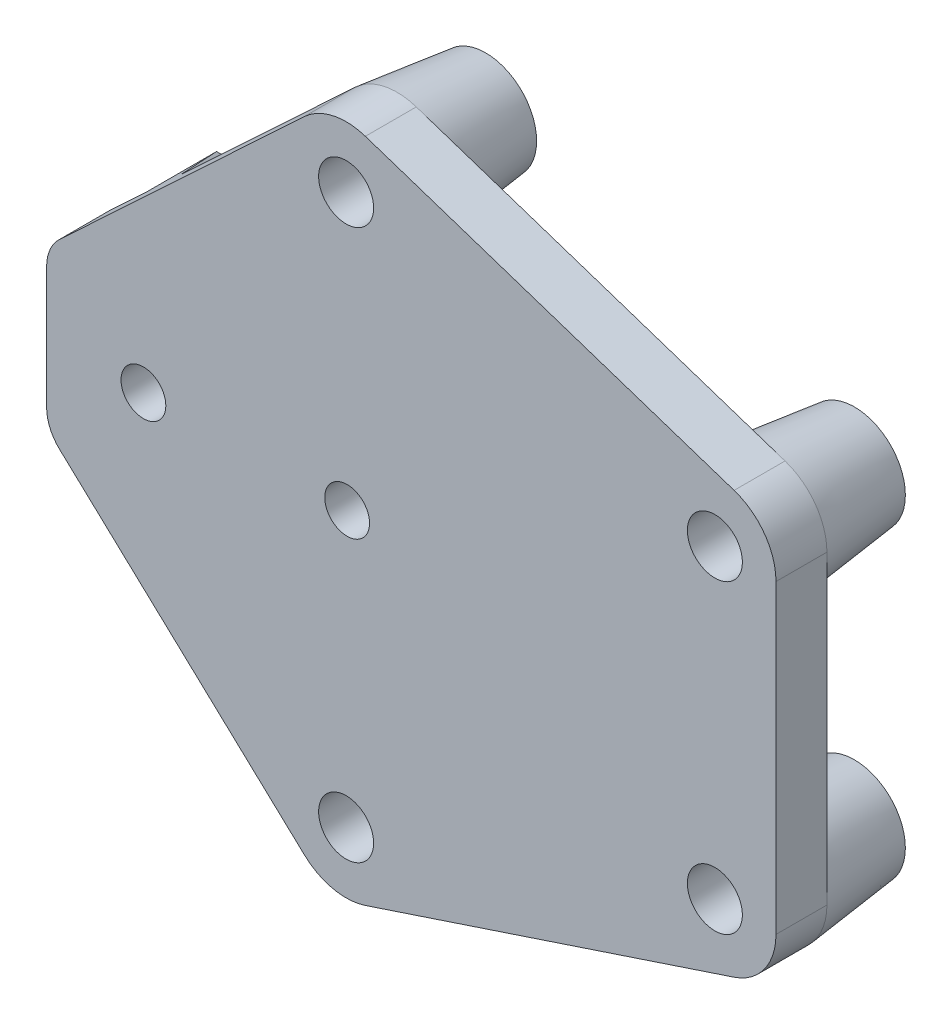
SolidWorks part; units mm, degrees
note: '?' marks a value the reader was unsure of. The reader was unsure of these and kept them because the rebuilt part matched: shared geometry of "草图4<3>", "草图1<4>".
ref_plane "前视基准面" through (0, 0, 0) normal (0, 0, 1) x (1, 0, 0)
ref_plane "上视基准面" through (0, 0, 0) normal (0, 1, 0) x (1, 0, 0)
ref_plane "右视基准面" through (0, 0, 0) normal (1, 0, 0) x (0, 0, -1)
sketch "草图1" plane through (0, 0, 0) normal (0, 0, 1) x (1, 0, 0)
  line L0 (-612.4365, 0) -> (30009.3904, 0) construction
  line L1 (-611.4109, 10) -> (30010.416, 10) construction
  line L2 (-607.9921, -10) -> (30013.8348, -10) construction
  line L3 (0, -612.4365) -> (0, 30009.3904) construction
  line L4 (-10, -612.4365) -> (-10, 30009.3904) construction
  line L5 (10, -614.6741) -> (10, 30007.1528) construction
  line L6 (-24.1, 27) -> (-24.1, -27) construction
  line L7 (-16.2121, 32.6952) -> (19.9879, 20.6952)
  line L8 (24.1, 15) -> (24.1, -15)
  line L9 (-32, -12.3) -> (-42.6171, -12.3)
  line L10 (-32, 12.3) -> (-42.6171, 12.3)
  line L11 (-32, 12.3) -> (-13, 12.3)
  line L12 (-32, 10.3) -> (-13, 10.3)
  line L13 (-13, 12.3) -> (-13, 10.3)
  line L14 (19.9879, -20.6952) -> (-16.2121, -32.6952)
  line L15 (-32, -10.3) -> (-13, -10.3)
  line L16 (-32, -12.3) -> (-13, -12.3)
  line L17 (-13, -12.3) -> (-13, -10.3)
  line L18 (-42.6171, 12.3) -> (-42.6171, 10.3)
  line L19 (-33.5, 10) -> (-33.5, -10) construction
  line L20 (-47.5, 6) -> (-47.5, -6)
  line L21 (-42.6171, 10.3) -> (-32, 10.3)
  line L22 (-42.6171, -12.3) -> (-42.6171, -10.3)
  line L23 (-22.1967, 31.3837) -> (-46.2312, 8.9225)
  line L24 (-22.1967, -31.3837) -> (-46.2312, -8.9225)
  line L25 (-42.6171, -10.3) -> (-32, -10.3)
  circle A0 centre (18.1, 27) radius 11.5 construction
  circle A1 centre (-18.1, 27) radius 11.5 construction
  circle A2 centre (-18.1, -27) radius 11.5 construction
  circle A3 centre (18.1, 15) radius 11.5 construction
  circle A4 centre (18.1, 15) radius 2.7
  circle A5 centre (-18.1, 27) radius 6
  circle A6 centre (-16, 14) radius 1.7 construction
  circle A7 centre (18.1, 15) radius 5 construction
  circle A8 centre (-18.1, 27) radius 2.7
  circle A9 centre (-18.1, -27) radius 2.7
  circle A10 centre (-18.1, 27) radius 5 construction
  circle A11 centre (-18.1, -27) radius 5 construction
  circle A12 centre (18.1, 15) radius 6
  circle A13 centre (18.1, -15) radius 5 construction
  circle A14 centre (-16, -14) radius 1.7 construction
  circle A15 centre (-18.1, -27) radius 6
  circle A16 centre (-18, 0) radius 2.2
  circle A17 centre (-38, 0) radius 2.2
  circle A18 centre (-31, 18) radius 2.2 construction
  circle A19 centre (-31, -18) radius 2.2 construction
  circle A20 centre (18.1, -15) radius 11.5 construction
  circle A21 centre (18.1, -15) radius 6
  circle A22 centre (18.1, -15) radius 2.7
  circle A23 centre (-18, 0) radius 4 construction
  arc A26 (-47.5, -6) -> (-43.525, -9.9999) centre (-43.5, -6) ccw
  arc A27 (-47.5, 6) -> (-43.2296, 9.9909) centre (-43.5, 6) cw
  point P48 (-31.5, 0)
  point P54 (-31.5, 0)
  point P82 (-47.5, -10)
  point P85 (-47.5, 10)
  dimension "D5" = 23
  dimension "D6" = 27
  dimension "D7" = 15
  dimension "D9" = 12
  dimension "D10" = 8
  dimension "D11" = 5.4
  dimension "D12" = 10
  dimension "D8" = 4.4
  dimension "D23" = 3.4
  dimension "D24" = 4.4
  dimension "D35" = 4
  dimension "D1" = 20
  dimension "D2" = 10
  dimension "D3" = 20
  dimension "D4" = 10
  dimension "D13" = 18.1
  dimension "D14" = 6
  dimension "D15" = 12
  dimension "D16" = 2
  dimension "D17" = 20.6
  dimension "D18" = 20
  dimension "D19" = 14.1
  dimension "D20" = 24.6
  dimension "D21" = 16
  dimension "D22" = 4
  dimension "D25" = 8
  dimension "D26" = 21
  dimension "D28" = 13
  dimension "D29" = 5
  dimension "D34" = 14
extrude "凸台-拉伸1" add sketch "草图1" along normal blind 5
ref_axis "基准轴1" through (-18.1, 27, 5) along (0, 0, -1)?
ref_axis "基准轴2" through (18.1, 15, 5) along (0, 0, -1)?
ref_plane "基准面2" through (6.2721, 18.9208, 0) normal (-0.3147, -0.9492, 0) x (-0.9492, 0.3147, 0)
sketch "草图4" plane through (6.2721, 18.9208, 0) normal (-0.3147, -0.9492, 0) x (-0.9492, 0.3147, 0)
  line L1 (-7.4608, 8.7) -> (-9.7608, 8.7)
  line L2 (25.6763, 0) -> (25.6763, 29798.822) construction
  line L3 (-6.4608, 0) -> (-7.4608, 8.7)
  line L4 (-9.7608, 0) -> (-6.4608, 0)
  line L5 (-9.7608, 8.7) -> (-9.7608, 0)
  line L10 (25.6763, -5) -> (25.6763, 0) construction
  line L11 (-12.4608, -4.4528) -> (-12.4608, 29794.3692) construction
  line L12 (-12.4608, -5) -> (-12.4608, 0) construction
  line L13 (25.6763, 0) -> (28.3763, 0) construction
  line L14 (30.9443, 0) -> (25.6763, 0) construction
  line L16 (28.3763, 0) -> (31.6763, 0)
  line L17 (31.6763, 0) -> (30.6763, 8.7)
  line L18 (30.6763, 8.7) -> (28.3763, 8.7)
  line L19 (28.3763, 8.7) -> (25.6763, 8.7) construction
  line L20 (28.3763, 8.7) -> (28.3763, 0)
  line L21 (25.6763, 8.7) -> (25.6763, 0) construction
  point P7 (0, 0)
  dimension "D2" = 2
  dimension "D3" = 5
  dimension "D7" = 2.7
  dimension "D8" = 6
  dimension "D9" = 8.7
  dimension "D10" = 5
revolve "旋转1" add sketch "草图4" angle 360 about L11
revolve "旋转2" add sketch "草图4<3>" angle 360 about L2
sketch "草图4<3>" plane through (6.2721, 18.9208, 0) normal (-0.3147, -0.9492, 0) x (-0.9492, 0.3147, 0) same geometry as "草图4"
mirror "镜向1" about plane through (0, 0, 0) normal (0, 1, 0) of "旋转2", "旋转1"
extrude "凸台-拉伸2" add sketch "草图1<4>" against normal blind 6.8
sketch "草图1<4>" plane through (0, 0, 0) normal (0, 0, 1) x (1, 0, 0) same geometry as "草图1"
chamfer "倒角1" distance 3 distance2 6.8 1 edges at (-27.8085, 12.3, 0)
chamfer "倒角2" distance 6.8 distance2 3 1 edges at (-27.8085, -12.3, 0)
sketch "草图5" [suppressed] plane through (0, 0, 0) normal (0, 0, -1) x (-1, 0, 0)
  line L0 (39.5, 5) -> (39.5, -5) construction
  line L1 (41, 5) -> (41, -5)
  line L2 (38, 5) -> (38, -5)
  arc A0 (41, 5) -> (38, 5) centre (39.5, 5) ccw
  arc A1 (38, -5) -> (41, -5) centre (39.5, -5) ccw
  circle A2 centre (39.5, -5) radius 1.5 construction
  point P4 (39.5, 0)
extrude "切除-拉伸1" [suppressed] cut sketch "草图5" against normal blind 2.5
